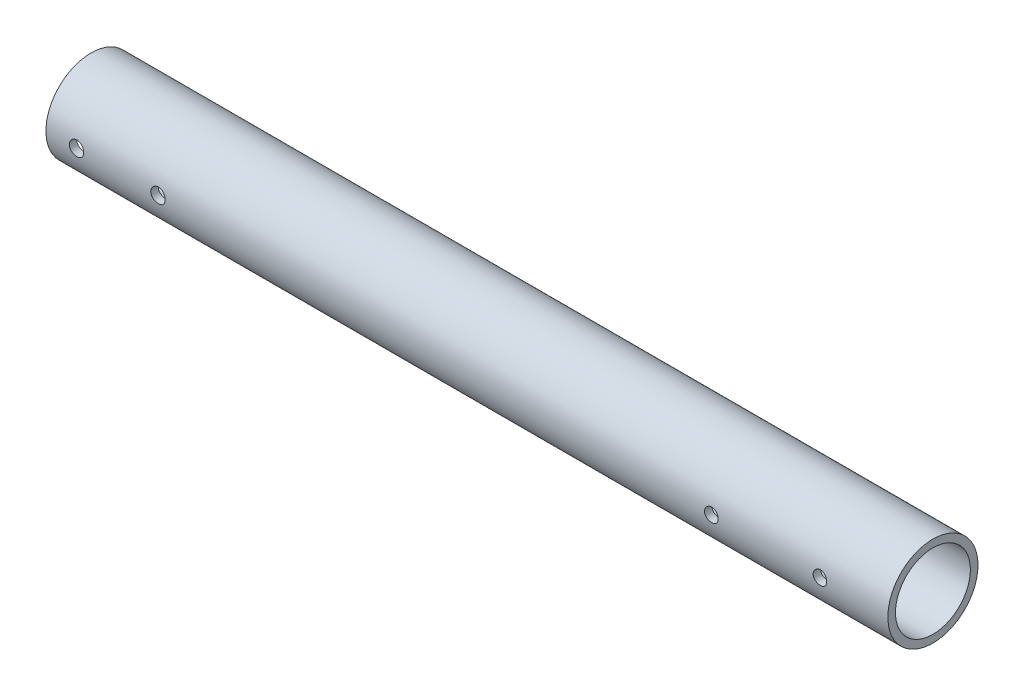
SolidWorks part; units mm, degrees
material "6061-T6 (SS)"
ref_plane "Front Plane" through (0, 0, 0) normal (0, 0, 1) x (1, 0, 0)
ref_plane "Top Plane" through (0, 0, 0) normal (0, 1, 0) x (1, 0, 0)
ref_plane "Right Plane" through (0, 0, 0) normal (1, 0, 0) x (0, 0, -1)
sketch "Sketch1" plane through (0, 0, 0) normal (1, 0, 0) x (0, 0, -1)
  circle A0 centre (0, 0) radius 21.082
  circle A1 centre (0, 0) radius 17.526
  dimension "D1" = 42.164
  dimension "D2" = 35.052
extrude "Boss-Extrude1" add sketch "Sketch1" along normal blind 196.85 and the other way blind 196.85
sketch "Sketch2" plane through (0, 0, 0) normal (0, 0, 1) x (1, 0, 0)
  line L0 (-196.85, 21.082) -> (-196.85, -21.082) construction
  circle A0 centre (-144.4625, 0) radius 3.3782
  circle A1 centre (-182.5625, 0) radius 3.3782
  dimension "D1" = 6.7564
  dimension "D2" = 14.2875
  dimension "D3" = 38.1
extrude "Cut-Extrude1" cut sketch "Sketch2" against normal through all both and the other way through all
sketch "Sketch3" plane through (0, 0, 0) normal (0, 0, 1) x (1, 0, 0)
  line L0 (196.85, -21.082) -> (196.85, 21.082) construction
  circle A0 centre (165.1, 0) radius 3.175
  circle A1 centre (114.3, 0) radius 3.175
  dimension "D1" = 6.35
  dimension "D2" = 6.35
  dimension "D3" = 31.75
  dimension "D4" = 50.8
extrude "Cut-Extrude2" cut sketch "Sketch3" along normal through all
